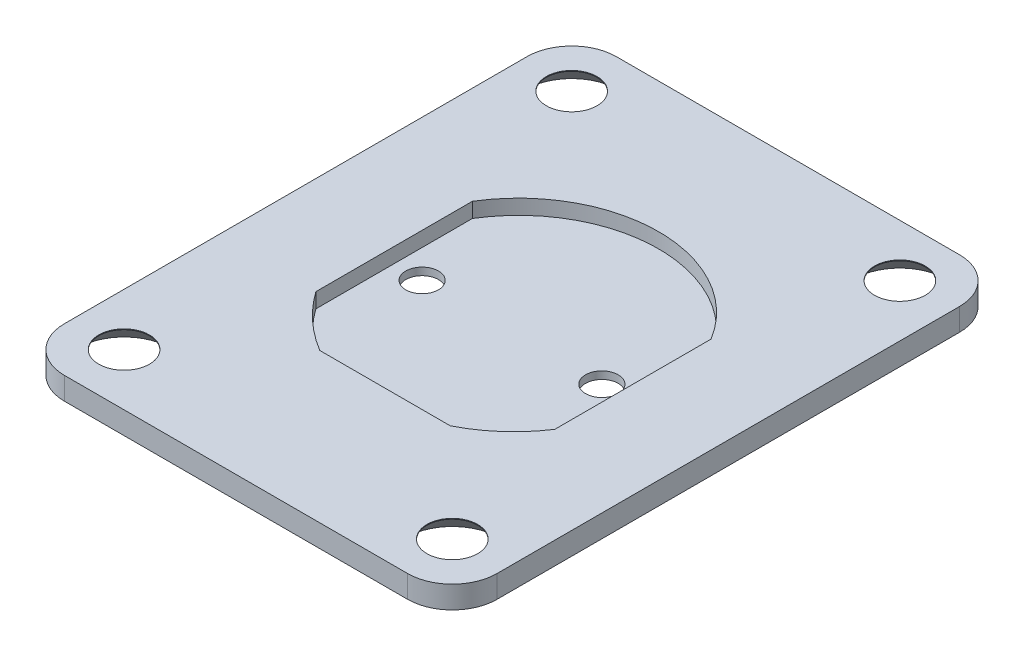
SolidWorks part; units mm, degrees
material "ABS"
ref_plane "Front Plane" through (0, 0, 0) normal (0, 0, 1) x (1, 0, 0)
ref_plane "Top Plane" through (0, 0, 0) normal (0, 1, 0) x (1, 0, 0)
ref_plane "Right Plane" through (0, 0, 0) normal (1, 0, 0) x (0, 0, -1)
sketch "Sketch5" plane through (0, 0, 0) normal (0, 1, 0) x (1, 0, 0)
  line L1 (14.5, -18.5) -> (-14.5, -18.5)
  line L2 (14.5, -18.5) -> (14.5, 18.5)
  line L3 (14.5, 18.5) -> (-14.5, 18.5)
  line L4 (-14.5, -18.5) -> (-14.5, 18.5)
  line L5 (14.5, -18.5) -> (-14.5, 18.5) construction
  line L6 (14.5, 18.5) -> (-14.5, -18.5) construction
  point P0 (0, 0)
  dimension "D1" = 37
  dimension "D2" = 29
extrude "Boss-Extrude3" add sketch "Sketch5" along normal blind 0.5
sketch "Sketch6" plane through (0, 0.5, 0) normal (0, 1, 0) x (1, 0, 0)
  line L0 (0, 0) -> (0, 5.1824) construction
  circle A0 centre (-6.025, 0) radius 1.095
  circle A1 centre (6.025, 0) radius 1.095
  dimension "D2" = 2.19
  dimension "D1" = 12.05
extrude "Cut-Extrude1" cut sketch "Sketch6" against normal through all both and the other way through all
sketch "Sketch7" plane through (0, 0.5, 0) normal (0, 1, 0) x (1, 0, 0)
  line L5 (8.0658, -5.2018) -> (8.0658, 5.2809)
  line L6 (-7.9342, -5.2115) -> (-7.9342, 5.2809)
  line L7 (4.3629, -8.4965) -> (-4.3854, -8.4965)
  line L9 (-14.5, -18.5) -> (14.5, -18.5)
  line L10 (-14.5, -18.5) -> (-14.5, 18.5)
  line L11 (-14.5, 18.5) -> (14.5, 18.5)
  line L12 (14.5, -18.5) -> (14.5, 18.5)
  line L13 (-14.5, 18.5) -> (-14.5, -18.5) construction
  line L15 (-14.5, -18.5) -> (14.5, -18.5) construction
  arc A3 (-7.9342, 5.2809) -> (8.0658, 5.2809) centre (0.0658, 0.3732) cw
  arc A4 (-7.9342, -5.2115) -> (-4.3854, -8.4965) centre (1.7365, 1.6768) ccw
  arc A5 (4.3629, -8.4965) -> (8.0658, -5.2018) centre (0.0516, 0.077) ccw
  line M18 (-14.5, 18.5) -> (-14.5, -18.5)
  line M19 (-14.5, -18.5) -> (14.5, -18.5)
  line M20 (14.5, -18.5) -> (14.5, 18.5)
  line M21 (14.5, 18.5) -> (-14.5, 18.5)
extrude "Boss-Extrude4" add sketch "Sketch7" along normal blind 1 contours A5 L7 A4 L6 A3 L5 M21 M18 M19 M20 region at (-14.0299, 0.5, 0)
fillet "Fillet1" radius 3 4 edges at (-14.5, 0.75, -18.5) (14.5, 0.75, -18.5) (-14.5, 0.75, 18.5) (14.5, 0.75, 18.5)
sketch "Sketch10" plane through (0, 0, 0) normal (0, -1, 0) x (1, 0, 0)
  line L1 (11, 15) -> (-11, 15) construction
  line L2 (11, 15) -> (11, -15) construction
  line L3 (11, -15) -> (-11, -15) construction
  line L4 (-11, 15) -> (-11, -15) construction
  line L5 (11, 15) -> (-11, -15) construction
  line L6 (11, -15) -> (-11, 15) construction
  point P0 (0, 0)
  dimension "D1" = 22
  dimension "D2" = 30
hole_wizard "CSK for M3 Countersunk Flat Head Screw1" positions "3DSketch1" profile "Sketch11" countersink size "M3" standard "ISO" end condition up to next
sketch3d "3DSketch1"
  point P0 (-11, 0, -15)
  point P3 (11, 0, -15)
  point P6 (11, 0, 15)
  point P9 (-11, 0, 15)
sketch "Sketch11" plane through (-11, 0, -15) normal (1, 0, 0) x (0, 0, -1)
  line L0 (0, 0) -> (0, 1.5)
  line L1 (0, 1.5) -> (1.7, 1.5)
  line L2 (1.7, 1.5) -> (1.7, 1.45)
  line L3 (1.7, 1.45) -> (3.15, 0)
  line L5 (3.15, 0) -> (0, 0)
  line L6 (-1.7, 1.45) -> (-3.15, 0) construction
  line L11 (0, -6.35) -> (0, 107.95) construction
  dimension "Thru Hole Dia." = 3.4
  dimension "Thru Hole Depth" = 1.5
  dimension "Near C'Sink Dia." = 6.3
  dimension "Near C'Sink Angle" = 90
ref_axis "Axis1" through (0, 1.575, 0) along (0, -1, 0)
